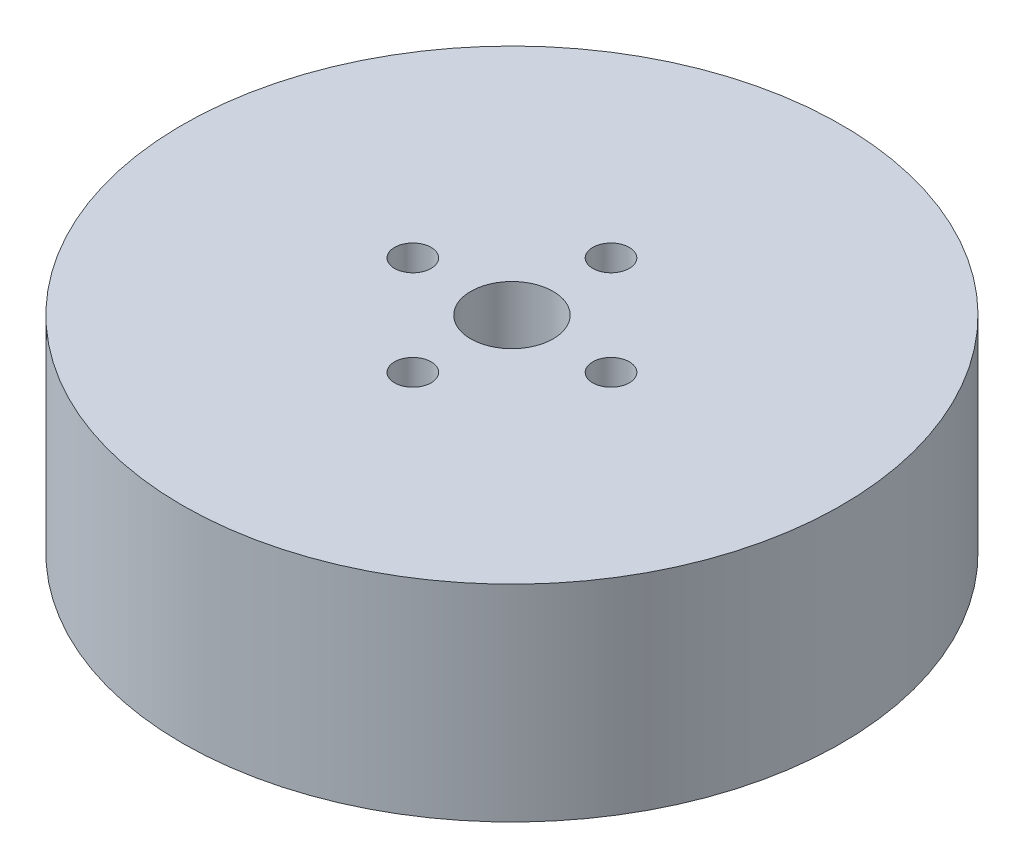
SolidWorks part; units mm, degrees
ref_plane "Front Plane" through (0, 0, 0) normal (0, 0, 1) x (1, 0, 0)
ref_plane "Top Plane" through (0, 0, 0) normal (0, 1, 0) x (1, 0, 0)
ref_plane "Right Plane" through (0, 0, 0) normal (1, 0, 0) x (0, 0, -1)
sketch "Sketch1" plane through (0, 0, 0) normal (0, 1, 0) x (1, 0, 0)
  circle A0 centre (0, 0) radius 40
  dimension "FLANGE_OD" = 80
extrude "Boss-Extrude1" add sketch "Sketch1" along normal blind 25
sketch "Sketch2" plane through (0, 0, 0) normal (0, 1, 0) x (1, 0, 0)
  circle A0 centre (0, 0) radius 5
  dimension "BORE_D" = 10
extrude "Cut-Extrude1" cut sketch "Sketch2" along normal through all
sketch "Sketch3" plane through (0, 25, 0) normal (0, 1, 0) x (1, 0, 0)
  circle A0 centre (0, 0) radius 12.0263 construction
  circle A1 centre (-12.0263, 0) radius 2.2184
  dimension "BOLT_D" = 4.4368
  dimension "BOLT_PCD" = 24.0526
extrude "Cut-Extrude2" cut sketch "Sketch3" against normal blind 18.7452
pattern_circular "CirPattern1" count 4 over 360 about axis through (0, 0, 0) along (0, 1, 0) of "Cut-Extrude2"
